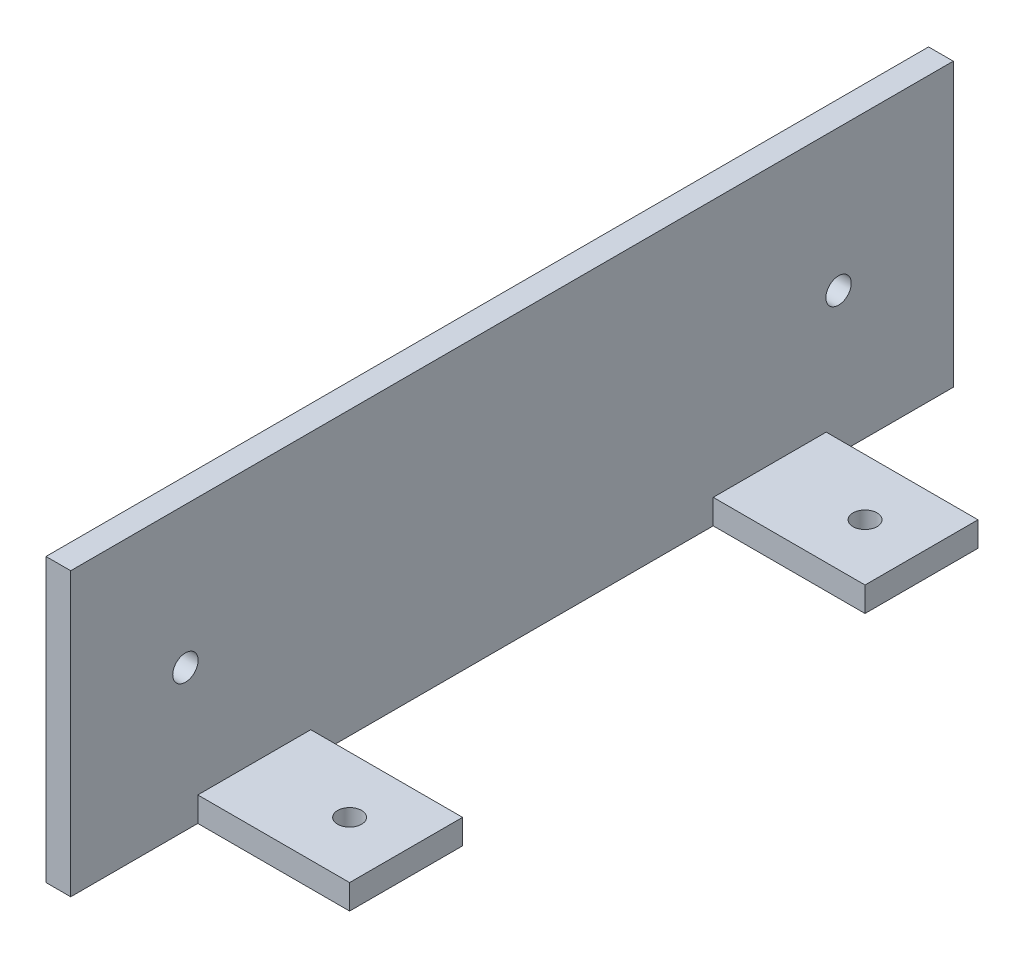
SolidWorks part; units mm, degrees
ref_plane "Front Plane" through (0, 0, 0) normal (0, 0, 1) x (1, 0, 0)
ref_plane "Top Plane" through (0, 0, 0) normal (0, 1, 0) x (1, 0, 0)
ref_plane "Right Plane" through (0, 0, 0) normal (1, 0, 0) x (0, 0, -1)
sketch "Sketch1" plane through (0, 0, 0) normal (0, 0, 1) x (1, 0, 0)
  line L0 (0, 0) -> (0, 40)
  line L1 (0, 40) -> (3.5, 40)
  line L2 (3.5, 40) -> (3.5, 3.5)
  line L3 (3.5, 3.5) -> (25, 3.5)
  line L4 (25, 3.5) -> (25, 0)
  line L5 (25, 0) -> (0, 0)
  dimension "D1" = 25
  dimension "D2" = 40
  dimension "D3" = 3.5
  dimension "D4" = 3.5
extrude "Boss-Extrude3" add sketch "Sketch1" along normal blind 62.5 and the other way blind 62.5 contours L5 L0 L1 L2 L3 L4
sketch "Sketch4" plane through (0, 0, 0) normal (-1, 0, 0) x (0, 0, 1)
  circle A0 centre (-46.25, 20) radius 1.8
  dimension "D2" = 3.6
extrude "Cut-Extrude1" cut sketch "Sketch4" against normal blind 62.5
sketch "Sketch5" plane through (0, 0, 0) normal (-1, 0, 0) x (0, 0, 1)
  line L1 (62.5, 0) -> (62.5, 40) construction
  line L2 (-62.5, 40) -> (62.5, 40) construction
  circle A0 centre (46.25, 20) radius 1.8
  dimension "D1" = 3.6
  dimension "D2" = 16.25
  dimension "D3" = 20
extrude "Cut-Extrude2" cut sketch "Sketch5" against normal blind 62.5
sketch "Sketch7" plane through (0, 3.5, 0) normal (0, 1, 0) x (1, 0, 0)
  line L0 (25, 62.5) -> (25, -62.5) construction
  line L1 (3.5, -62.5) -> (25, -62.5)
  line L2 (3.5, -62.5) -> (3.5, -44.5)
  line L3 (3.5, -44.5) -> (25, -44.5)
  line L4 (25, -62.5) -> (25, -44.5)
  dimension "D1" = 18
extrude "Cut-Extrude5" cut sketch "Sketch7" against normal blind 62.5
sketch "Sketch10" plane through (0, 3.5, 0) normal (0, 1, 0) x (1, 0, 0)
  line L0 (25, 62.5) -> (25, -44.5) construction
  line L1 (3.5, 62.5) -> (25, 62.5)
  line L2 (3.5, 62.5) -> (3.5, 44.5)
  line L3 (3.5, 44.5) -> (25, 44.5)
  line L4 (25, 62.5) -> (25, 44.5)
  dimension "D1" = 18
extrude "Cut-Extrude7" cut sketch "Sketch10" against normal blind 62.5
sketch "Sketch13" plane through (0, 3.5, 0) normal (0, 1, 0) x (1, 0, 0)
  line L0 (3.5, 44.5) -> (3.5, -44.5) construction
  line L1 (3.5, 0) -> (25, 0)
  line L2 (3.5, 0) -> (3.5, -28.5)
  line L3 (3.5, -28.5) -> (25, -28.5)
  line L4 (25, 0) -> (25, -28.5)
  line L5 (25, 44.5) -> (25, -44.5) construction
  dimension "D1" = 28.5
extrude "Cut-Extrude9" cut sketch "Sketch13" against normal blind 62.5
sketch "Sketch18" plane through (0, 3.5, 0) normal (0, 1, 0) x (1, 0, 0)
  line L0 (3.5, 44.5) -> (3.5, 0) construction
  line L1 (25, 0) -> (3.5, 0)
  line L2 (25, 0) -> (25, 28.5)
  line L3 (25, 28.5) -> (3.5, 28.5)
  line L4 (3.5, 0) -> (3.5, 28.5)
  dimension "D1" = 28.5
extrude "Cut-Extrude10" cut sketch "Sketch18" against normal blind 62.5
sketch "Sketch20" plane through (0, 3.5, 0) normal (0, 1, 0) x (1, 0, 0)
  line L0 (3.5, 44.5) -> (25, 44.5) construction
  line L2 (25, 44.5) -> (25, 28.5) construction
  circle A0 centre (17, 36.5) radius 1.7
  dimension "D1" = 3.4
  dimension "D2" = 8
  dimension "D3" = 8
extrude "Cut-Extrude11" cut sketch "Sketch20" against normal blind 62.5
sketch "Sketch21" plane through (0, 3.5, 0) normal (0, 1, 0) x (1, 0, 0)
  line L0 (3.5, -28.5) -> (25, -28.5) construction
  line L1 (25, -28.5) -> (25, -44.5) construction
  circle A0 centre (17, -36.5) radius 1.7
  dimension "D1" = 3.4
  dimension "D2" = 8
  dimension "D3" = 8
extrude "Cut-Extrude12" cut sketch "Sketch21" against normal blind 62.5
